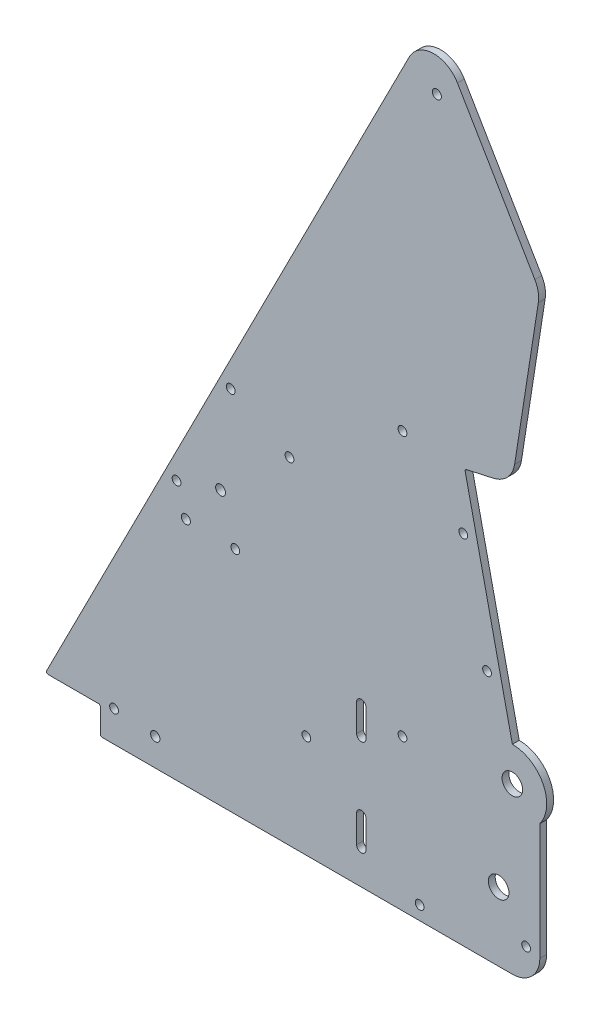
SolidWorks part; units mm, degrees
other "Markup1"
sketch "Sketch5"
ref_plane "Front Plane" through (0, 0, 0) normal (0, 0, 1) x (1, 0, 0)
ref_plane "Top Plane" through (0, 0, 0) normal (0, 1, 0) x (1, 0, 0)
ref_plane "Right Plane" through (0, 0, 0) normal (1, 0, 0) x (0, 0, -1)
sketch "Sketch1" plane through (0, 0, 0) normal (0, 0, 1) x (1, 0, 0)
  line L1 (228.6, -12.7) -> (228.6, 53.975)
  line L2 (178.7547, 351.4131) -> (0, 0)
  line L3 (228.6, 266.7) -> (178.7547, 351.4131)
  line L5 (0, 0) -> (25.4, 0)
  line L6 (25.4, 0) -> (25.4, -12.7)
  line L7 (25.4, -12.7) -> (228.6, -12.7)
  line L9 (215.9, 79.375) -> (193.9097, 178.5667)
  line L10 (193.9097, 178.5667) -> (215.6079, 183.377)
  line L11 (215.6079, 183.377) -> (228.6, 266.7)
  arc A0 (228.6, 53.975) -> (215.9, 79.375) centre (215.9, 63.5) ccw
  dimension "D7" = 12.7
  dimension "D8" = 76.2
  dimension "D10" = 31.75
  dimension "D2" = 279.4
  dimension "D3" = 25.4
  dimension "D4" = 215.9
  dimension "D5" = 394.2644
  dimension "D6" = 203.2
  dimension "D9" = 63.039
  dimension "D11" = 101.6
  dimension "D12" = 12.5
  dimension "D13" = 22.225
extrude "Boss-Extrude1" add sketch "Sketch1" along normal blind 3.175
sketch "Sketch2" plane through (0, 0, 3.175) normal (0, 0, 1) x (1, 0, 0)
  line L0 (178.7547, 351.4131) -> (0, 0) construction
  line L1 (25.4, -12.7) -> (228.6, -12.7) construction
  line L2 (215.9, 79.375) -> (193.9097, 178.5667) construction
  line L3 (193.9097, 178.5667) -> (215.6079, 183.377) construction
  line L4 (215.9, 79.375) -> (193.9097, 178.5667) construction
  line L10 (228.6, -12.7) -> (228.6, 53.975) construction
  circle A0 centre (64.9432, 94.0578) radius 2.0955
  circle A1 centre (180.975, 322.1643) radius 2.0955
  circle A2 centre (81.0071, 113.733) radius 2.286
  circle A3 centre (193.2078, 152.3944) radius 2.032
  circle A4 centre (215.9, 63.5) radius 4.7625
  circle A7 centre (173.0375, -6.35) radius 2.032
  circle A8 centre (204.203, 102.7985) radius 2.032
  circle A26 centre (209.55, 19.05) radius 4.7625
  circle A28 centre (60.6578, 107.342) radius 2.032
  arc A30 (228.6, 53.975) -> (215.9, 79.375) centre (215.9, 63.5) ccw construction
  circle A31 centre (165.1, 179.3875) radius 2.032
  circle A32 centre (87.825, 93.5227) radius 2.032
  circle A33 centre (112.8724, 142.7633) radius 2.032
  circle A34 centre (85.7052, 156.5826) radius 2.032
  dimension "D3" = 4.191
  dimension "D5" = 4.191
  dimension "D9" = 4.572
  dimension "D20" = 9.525
  dimension "D23" = 9.525
  dimension "D18" = 4.064
  dimension "D26" = 4.064
  dimension "D14" = 4.064
  dimension "D10" = 4.064
  dimension "D2" = 15.24
  dimension "D6" = 15.24
  dimension "D7" = 25.4
  dimension "D8" = 20.6375
  dimension "D21" = 44.45
  dimension "D22" = 6.35
  dimension "D19" = 160.3375
  dimension "D24" = 44.45
  dimension "D25" = 6.35
  dimension "D27" = 25.4
  dimension "D28" = 50.8
  dimension "D29" = 6.35
  dimension "D17" = 6.35
  dimension "D33" = 55.5625
  dimension "D15" = 114.3
  dimension "D4" = 180.975
extrude "Cut-Extrude1" cut sketch "Sketch2" against normal through all
sketch "Sketch7" plane through (0, 0, 3.175) normal (0, 0, 1) x (1, 0, 0)
  line L0 (146.05, 3.175) -> (146.05, 15.875) construction
  line L1 (143.891, 3.175) -> (143.891, 15.875)
  line L2 (148.209, 3.175) -> (148.209, 15.875)
  line L3 (146.05, 47.625) -> (146.05, 60.325) construction
  line L4 (143.891, 47.625) -> (143.891, 60.325)
  line L5 (148.209, 47.625) -> (148.209, 60.325)
  line L6 (25.4, -12.7) -> (228.6, -12.7) construction
  line L12 (228.6, -12.7) -> (228.6, 53.975) construction
  line L13 (25.4, -12.7) -> (228.6, -12.7) construction
  arc A0 (143.891, 3.175) -> (148.209, 3.175) centre (146.05, 3.175) ccw
  arc A1 (148.209, 15.875) -> (143.891, 15.875) centre (146.05, 15.875) ccw
  arc A2 (143.891, 47.625) -> (148.209, 47.625) centre (146.05, 47.625) ccw
  arc A3 (148.209, 60.325) -> (143.891, 60.325) centre (146.05, 60.325) ccw
  circle A8 centre (50.8, 0) radius 2.159
  point P2 (146.05, 9.525)
  point P9 (146.05, 53.975)
  dimension "D1" = 4.318
  dimension "D5" = 4.318
  dimension "D2" = 12.7
  dimension "D3" = 12.7
  dimension "D4" = 44.45
  dimension "D6" = 95.25
  dimension "D7" = 82.55
  dimension "D8" = 15.875
  dimension "D9" = 12.7
extrude "Cut-Extrude2" cut sketch "Sketch7" against normal through all
sketch "Sketch10" plane through (0, 0, 3.175) normal (0, 0, 1) x (1, 0, 0)
  circle A0 centre (120.65, 34.925) radius 2.032
  circle A1 centre (165.1, 57.15) radius 2.032
  dimension "D1" = 4.064
  dimension "D3" = 34.925
  dimension "D2" = 120.65
  dimension "D4" = 63.5
  dimension "D5" = 69.85
extrude "Cut-Extrude3" cut sketch "Sketch10" against normal up to next
fillet "Fillet1" radius 12.7 4 edges at (228.6, -12.7, 1.5875) (178.7547, 351.4131, 1.5875) (215.6079, 183.377, 1.5875) (228.6, 266.7, 1.5875)
fillet "Fillet2" radius 0.7937 4 edges at (25.4, -12.7, 1.5875) (25.4, 0, 1.5875) (193.9097, 178.5667, 1.5875) (0, 0, 1.5875)
sketch "Sketch12" plane through (0, 0, 3.175) normal (0, 0, 1) x (1, 0, 0)
  circle A0 centre (31.75, 1.5875) radius 2.032
  circle A1 centre (173.0375, -6.35) radius 2.032
  circle A2 centre (222.25, 1.5875) radius 2.032
  dimension "D1" = 4.064
extrude "Cut-Extrude5" cut sketch "Sketch12" against normal through all
equation "\"D6@Sketch2\"=\"D2@Sketch2\""
